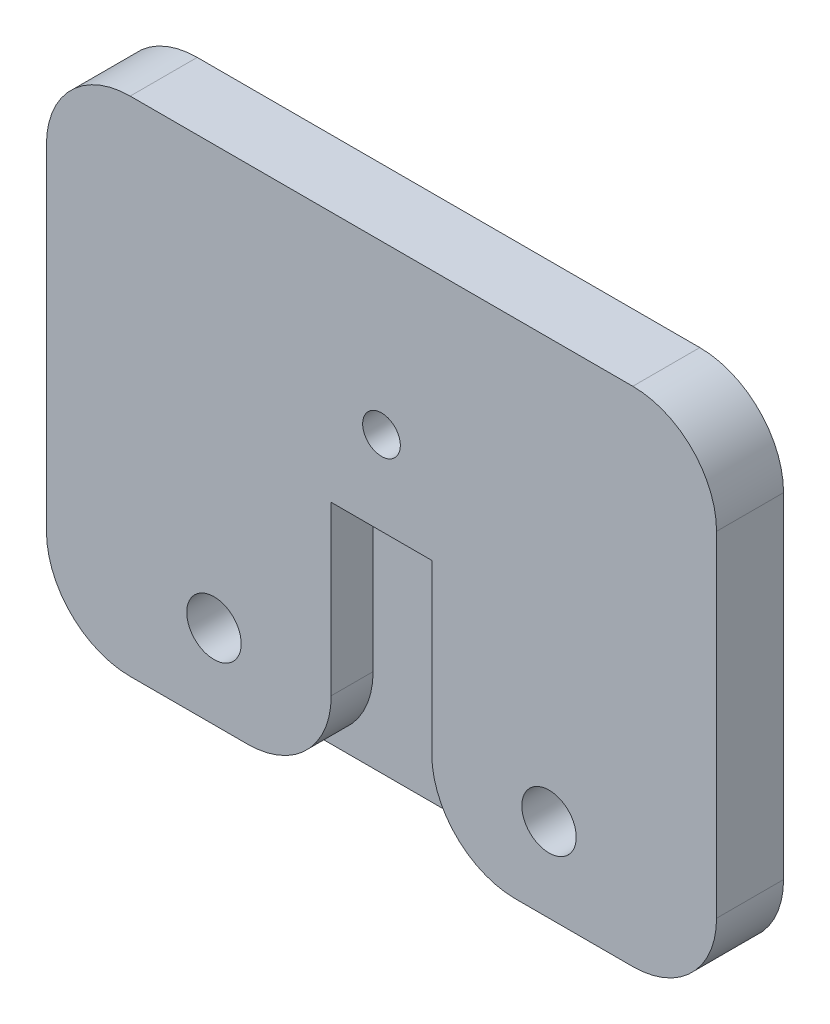
SolidWorks part; units mm, degrees
ref_plane "前视基准面" through (0, 0, 0) normal (0, 0, 1) x (1, 0, 0)
ref_plane "上视基准面" through (0, 0, 0) normal (0, 1, 0) x (1, 0, 0)
ref_plane "右视基准面" through (0, 0, 0) normal (1, 0, 0) x (0, 0, -1)
sketch "草图1" plane through (0, 0, 0) normal (0, 0, 1) x (1, 0, 0)
  line L0 (0, 30) -> (0, -10) construction
  line L1 (30, 30) -> (-30, 30)
  line L2 (40, 20) -> (40, -20)
  line L3 (30, -30) -> (-30, -30)
  line L4 (-40, 20) -> (-40, -20)
  line L5 (40, 30) -> (-40, -30) construction
  line L6 (40, -30) -> (-40, 30) construction
  line L7 (0, -10) -> (0, -20) construction
  line L8 (-20, -20) -> (20, -20) construction
  circle A0 centre (0, 10) radius 5
  circle A1 centre (0, 10) radius 2.25
  circle A2 centre (-20, -20) radius 3.25
  circle A3 centre (20, -20) radius 3.25
  arc A4 (40, -20) -> (30, -30) centre (30, -20) cw
  arc A5 (-30, -30) -> (-40, -20) centre (-30, -20) cw
  arc A6 (30, 30) -> (40, 20) centre (30, 20) cw
  arc A7 (-30, 30) -> (-40, 20) centre (-30, 20) ccw
  point P0 (0, 0)
  point P15 (0, -20)
  dimension "D4" = 10
  dimension "D5" = 4.5
  dimension "D8" = 6.5
  dimension "D9" = 6.5
  dimension "D10" = 10
  dimension "D1" = 60
  dimension "D2" = 80
  dimension "D3" = 40
  dimension "D6" = 10
  dimension "D7" = 20
extrude "凸台-拉伸1" add sketch "草图1" along normal blind 8 contours L1 A7 L4 A5 L3 A4 L2 A6 A0 A2 A3 | A0 A1 region at (0, 0.1186, 0) region at (-4.8586, 10, 0)
extrude "切除-拉伸1" cut sketch "草图1<3>" along normal blind 3.3 contours A0 A1 region at (-4.8586, 10, 0)
sketch "草图1<3>" plane through (0, 0, 0) normal (0, 0, 1) x (1, 0, 0) same geometry as "草图1"
sketch "草图2" plane through (0, 0, 8) normal (0, 0, 1) x (1, 0, 0)
  line L0 (-6, -30) -> (6, -30)
  line L1 (30, -30) -> (-30, -30) construction
  line L2 (6, -30) -> (6, 0)
  line L3 (6, 0) -> (-6, 0)
  line L4 (-6, 0) -> (-6, -30)
  point P5 (0, -30)
  dimension "D1" = 30
extrude "切除-拉伸2" cut sketch "草图2" against normal blind 5
fillet "圆角1" radius 10 2 edges at (-6, -30, 5.5) (6, -30, 5.5)
